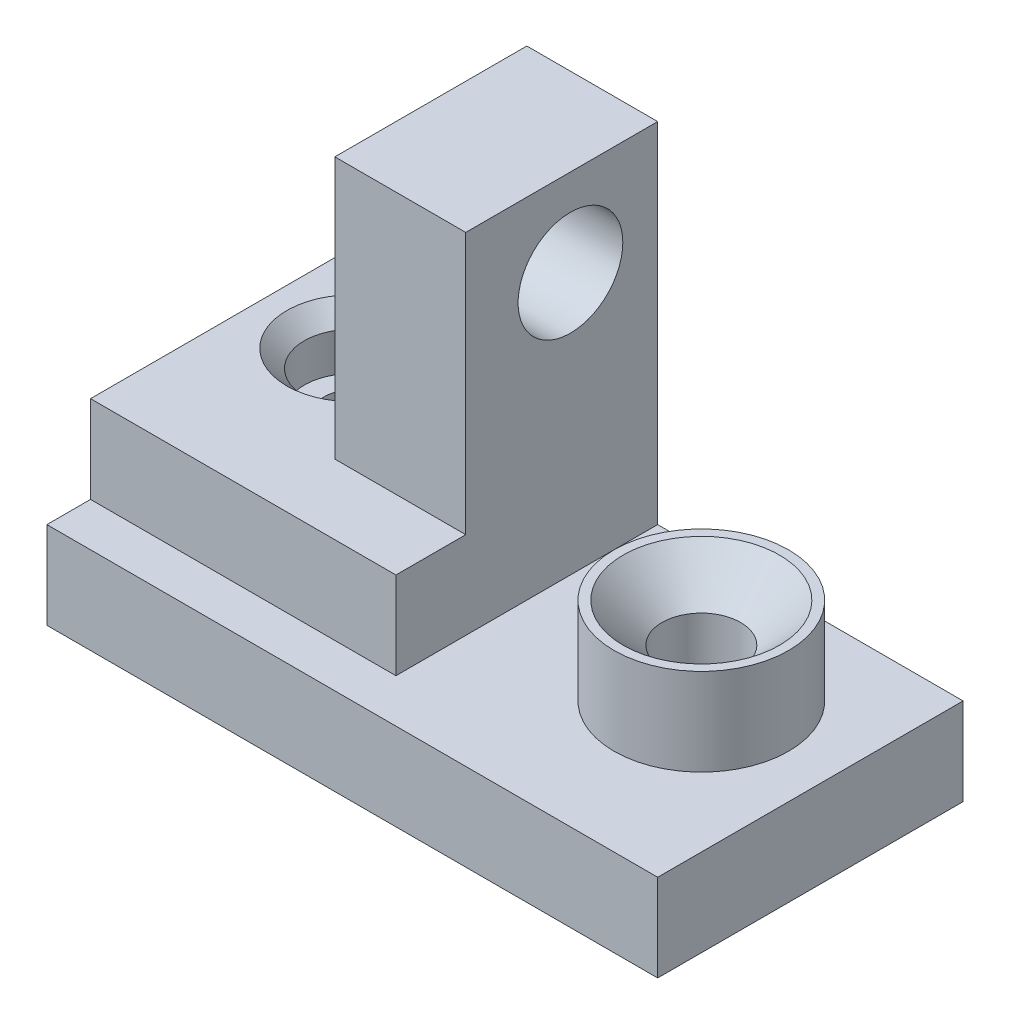
SolidWorks part; units mm, degrees
material "1060 Alloy"
ref_plane "Front Plane" through (0, 0, 0) normal (0, 0, 1) x (1, 0, 0)
ref_plane "Top Plane" through (0, 0, 0) normal (0, 1, 0) x (1, 0, 0)
ref_plane "Right Plane" through (0, 0, 0) normal (1, 0, 0) x (0, 0, -1)
sketch "Sketch1" plane through (0, 0, 0) normal (0, 1, 0) x (1, 0, 0)
  line L1 (0, 0) -> (70, 0)
  line L2 (0, 0) -> (0, 35)
  line L3 (0, 35) -> (70, 35)
  line L4 (70, 0) -> (70, 35)
  line L5 (0, 35) -> (35, 35)
  line L6 (0, 35) -> (0, 5)
  line L7 (0, 5) -> (35, 5)
  line L8 (35, 35) -> (35, 5)
  line L9 (20, 35) -> (35, 35)
  line L10 (20, 35) -> (20, 13)
  line L11 (20, 13) -> (35, 13)
  line L12 (35, 35) -> (35, 13)
  circle A0 centre (55, 20) radius 10
  dimension "D9" = 20
  dimension "D1" = 70
  dimension "D2" = 35
  dimension "D3" = 35
  dimension "D4" = 30
  dimension "D5" = 15
  dimension "D6" = 22
  dimension "D7" = 15
  dimension "D8" = 15
extrude "Boss-Extrude1" add sketch "Sketch1" along normal blind 10 contours L3 L8 L7 L2 L1 L4 region at (46.1359, 0, -14.3592)
extrude "Boss-Extrude2" add sketch "Sketch1<3>" along normal blind 20 contours L11 L10 L3 L2 L7 L8 | A0 region at (12.9167, 0, -18.1667) region at (55, 0, -20)
sketch "Sketch1<3>" plane through (0, 0, 0) normal (0, 1, 0) x (1, 0, 0) same geometry as "Sketch1"
extrude "Boss-Extrude3" add sketch "Sketch1<4>" along normal blind 50 contours L10 L11 L8 L5 region at (27.5, 0, -24)
sketch "Sketch1<4>" plane through (0, 0, 0) normal (0, 1, 0) x (1, 0, 0) same geometry as "Sketch1"
hole_wizard "CSK for M8 Hex Socket Countersunk Cap Screw1" positions "3DSketch2" profile "Sketch3" countersink size "M8" standard "ISO" end condition through all
sketch3d "3DSketch2"
  line L0 (55, 20, -20) -> (55, 10, -20) construction
  point P0 (55, 20, -20)
  point P5 (0, 0, 0)
sketch "Sketch3" plane through (55, 20, -20) normal (1, 0, 0) x (0, 0, 1)
  line L0 (0, 0) -> (0, 20)
  line L1 (0, 20) -> (4.5, 20)
  line L2 (4.5, 20) -> (4.5, 4.46)
  line L3 (4.5, 4.46) -> (8.96, 0)
  line L5 (8.96, 0) -> (0, 0)
  line L6 (-4.5, 4.46) -> (-8.96, 0) construction
  line L11 (0, -6.35) -> (0, 107.95) construction
  dimension "Thru Hole Dia." = 9
  dimension "Thru Hole Depth" = 20
  dimension "Near C'Sink Dia." = 17.92
  dimension "Near C'Sink Angle" = 90
hole_wizard "CBORE for M6 Hex Socket Head Cap Screw1" positions "Sketch4" profile "Sketch5" counterbore size "M6" standard "ISO"
sketch "Sketch4" plane through (0, 20, 0) normal (0, 1, 0) x (1, 0, 0)
  line L0 (0, 5) -> (0, 35) construction
  line L1 (0, 35) -> (20, 35) construction
  point P0 (10, 25)
  dimension "D1" = 10
  dimension "D2" = 10
sketch "Sketch5" plane through (10, 20, -25) normal (1, 0, 0) x (0, 0, 1)
  line L0 (0, 0) -> (0, 11.9228)
  line L1 (0, 11.9228) -> (3.2, 10)
  line L2 (3.2, 10) -> (3.2, 6.4)
  line L3 (3.2, 6.4) -> (5.5, 6.4)
  line L5 (5.5, 6.4) -> (5.5, 2)
  line L6 (5.5, 2) -> (7.5, 0)
  line L7 (7.5, 0) -> (0, 0)
  line L8 (-5.5, 2) -> (-7.5, 0) construction
  line L10 (0, 11.9228) -> (-3.2, 10) construction
  line L11 (0, -6.35) -> (0, 107.95) construction
  dimension "Hole Dia." = 6.4
  dimension "Hole Depth" = 10
  dimension "C'Bore Dia." = 11
  dimension "C'Bore Depth" = 6.4
  dimension "Near C'Sink Dia." = 15
  dimension "Near C'Sink Angle" = 90
  dimension "Drill Angle" = 118
hole_wizard "Tap Drill for M8 Tap1" positions "3DSketch3" profile "Sketch7" hole size "M8" standard "ISO"
sketch3d "3DSketch3"
  line L0 (35, 50, -35) -> (35, 10, -35) construction
  line L1 (35, 50, -35) -> (35, 50, -13) construction
  point P0 (35, 40, -25)
  dimension "D1" = 10
  dimension "D2" = 10
sketch "Sketch7" plane through (35, 40, -25) normal (0, 1, 0) x (0, 0, -1)
  line L0 (0, 0) -> (0, 13.4641)
  line L1 (0, 13.4641) -> (6, 10)
  line L2 (6, 10) -> (6, 0)
  line L5 (6, 0) -> (0, 0)
  line L10 (0, 13.4641) -> (-6, 10) construction
  line L11 (0, -6.35) -> (0, 107.95) construction
  dimension "Hole Dia." = 12
  dimension "Hole Depth" = 10
  dimension "Drill Angle" = 120
